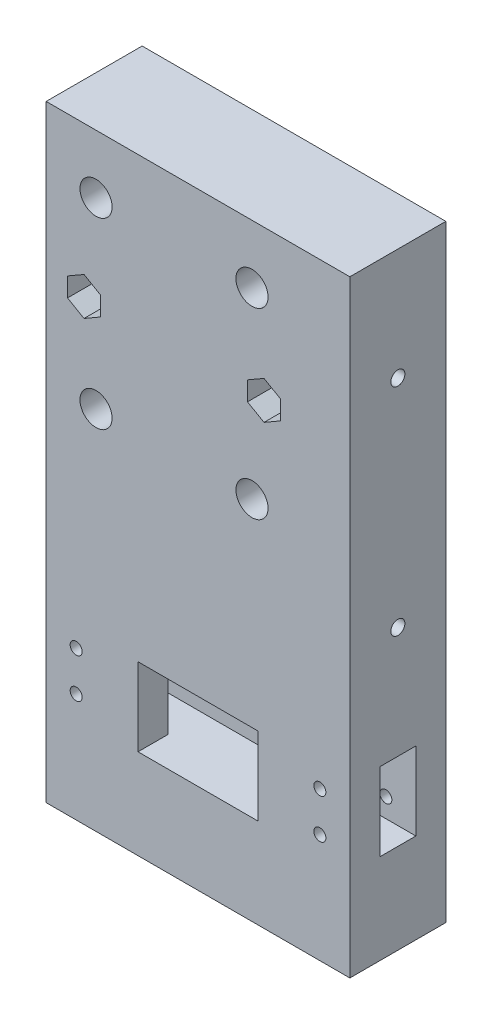
SolidWorks part; units mm, degrees
other "Markup1"
sketch "Sketch8" plane through (21.3115, 25, 0) normal (0.306, 0.1864, -0.9336) x (-0.9512, 0.0181, -0.3081)
ref_plane "Front Plane" through (0, 0, 0) normal (0, 0, 1) x (1, 0, 0)
ref_plane "Top Plane" through (0, 0, 0) normal (0, 1, 0) x (1, 0, 0)
ref_plane "Right Plane" through (0, 0, 0) normal (1, 0, 0) x (0, 0, -1)
sketch "Sketch1" plane through (0, 0, 0) normal (0, 0, 1) x (1, 0, 0)
  line L0 (0, 25) -> (0, -25) construction
  line L1 (21.3115, 25) -> (-21.3115, 25)
  line L2 (21.3115, 25) -> (21.3115, -25)
  line L3 (21.3115, -25) -> (-21.3115, -25)
  line L4 (-21.3115, 25) -> (-21.3115, -25)
  line L5 (21.3115, 25) -> (-21.3115, -25) construction
  line L6 (21.3115, -25) -> (-21.3115, 25) construction
  line L7 (-21.3115, 0) -> (21.3115, 0) construction
  circle A0 centre (-13, -15.25) radius 2.677
  circle A1 centre (13, -15.25) radius 2.677
  circle A2 centre (13, 15.25) radius 2.677
  circle A3 centre (-13, 15.25) radius 2.677
  point P0 (0, 0)
  dimension "D1" = 30.5
  dimension "D2" = 26
  dimension "D3" = 50
extrude "Boss-Extrude1" add sketch "Sketch1" along normal blind 16
sketch "Sketch2" plane through (0, 0, 0) normal (0, 0, 1) x (1, 0, 0)
  circle A0 centre (0, 0) radius 11
  dimension "D1" = 22
extrude "Cut-Extrude2" cut sketch "Sketch2" along normal blind 11
sketch "Sketch3" plane through (0, 0, 0) normal (0, 0, -1) x (-1, 0, 0)
  line L0 (0, 0) -> (-18.0234, 0) construction
  line L1 (0, 0) -> (0, 5.0894) construction
  circle A0 centre (-15, 0) radius 1.75
  circle A1 centre (15, 0) radius 1.75
  dimension "D1" = 15
  dimension "D2" = 3.5
extrude "Cut-Extrude3" cut sketch "Sketch3" against normal blind 10
sketch "Sketch9" plane through (0, 0, 0) normal (0, 0, -1) x (-1, 0, 0)
  line L0 (0, -11) -> (0, 11) construction
  line L1 (-15, 3.1754) -> (-17.75, 1.5877)
  line L2 (-17.75, 1.5877) -> (-17.75, -1.5877)
  line L3 (-17.75, -1.5877) -> (-15, -3.1754)
  line L4 (-15, -3.1754) -> (-12.25, -1.5877)
  line L5 (-12.25, -1.5877) -> (-12.25, 1.5877)
  line L6 (-12.25, 1.5877) -> (-15, 3.1754)
  line L7 (12.25, 1.5877) -> (15, 3.1754)
  line L8 (12.25, -1.5877) -> (12.25, 1.5877)
  line L9 (15, -3.1754) -> (12.25, -1.5877)
  line L10 (17.75, -1.5877) -> (15, -3.1754)
  line L11 (17.75, 1.5877) -> (17.75, -1.5877)
  line L12 (15, 3.1754) -> (17.75, 1.5877)
  circle A0 centre (-15, 0) radius 2.75 construction
  circle A1 centre (0, 0) radius 11 construction
  point P1 (-17.75, 0)
  dimension "D1" = 5.5
extrude "Cut-Extrude6" cut sketch "Sketch9" against normal through all from offset 5 offset against normal yes
sketch "Sketch30" plane through (0, -25, 0) normal (0, -1, 0) x (1, 0, 0)
  line L1 (-21.3115, 16) -> (21.3115, 16)
  line L2 (-21.3115, 16) -> (-21.3115, 0)
  line L3 (-21.3115, 0) -> (21.3115, 0)
  line L4 (21.3115, 16) -> (21.3115, 0)
extrude "Boss-Extrude8" add sketch "Sketch30" along normal blind 20.23
sketch "Sketch10" plane through (0, 0, 0) normal (0, 0, 1) x (1, 0, 0)
  line L0 (21.3115, -45.23) -> (-21.3115, -45.23)
  line L2 (-21.3115, -45.23) -> (-21.3115, -61.23)
  line L3 (-21.3115, -61.23) -> (21.3115, -61.23)
  line L4 (21.3115, -61.23) -> (21.3115, -45.23)
  dimension "D1" = 16
extrude "Boss-Extrude2" add sketch "Sketch10" along normal up to surface (16 mm away) up to face at (15, 0, 16)
sketch "Sketch14" plane through (-21.3115, 0, 0) normal (-1, 0, 0) x (0, 0, 1)
  line L0 (16, -61.23) -> (0, -61.23) construction
  line L1 (5, -61.23) -> (11, -61.23)
  line L2 (5, -61.23) -> (5, -48.23)
  line L3 (5, -48.23) -> (11, -48.23)
  line L4 (11, -61.23) -> (11, -48.23)
  line L7 (0, -61.23) -> (16, -61.23) construction
  point P6 (8, -61.23)
  point P7 (8, -61.23)
  dimension "D1" = 13
  dimension "D2" = 6
extrude "Cut-Extrude7" cut sketch "Sketch14" against normal through all
sketch "Sketch16" plane through (21.3115, 0, 0) normal (1, 0, 0) x (0, 0, -1)
  line L0 (-8, -48.23) -> (-8, 25)
  line L1 (-11, -48.23) -> (-5, -48.23) construction
  line L2 (-16, 25) -> (0, 25) construction
  line L4 (-16, 25) -> (0, 25)
  line L5 (-16, 25) -> (-16, -48.23)
  line L6 (-16, -48.23) -> (0, -48.23)
  line L7 (0, 25) -> (0, -48.23)
  line M6 (-11, -48.23) -> (-5, -48.23)
  line M9 (0, -61.23) -> (0, 25)
  line M10 (0, 25) -> (-16, 25)
  line M11 (-16, 25) -> (-16, -61.23)
extrude "Boss-Extrude3" add sketch "Sketch16" along normal blind 8 contours L6 L0 M11 M6 M10 | L6 L0 M6 M9 M10 region at (21.3115, -11.615, 12) region at (21.3115, -11.615, 4)
sketch "Sketch17" plane through (29.3115, 0, 0) normal (1, 0, 0) x (0, 0, -1)
  line L0 (-8, -48.23) -> (-8, 25)
  line L1 (-16, -48.23) -> (0, -48.23) construction
  line L2 (0, 25) -> (-16, 25) construction
  line L3 (-8, -11.615) -> (0, -11.615)
  line L4 (0, -48.23) -> (0, 25) construction
  circle A0 centre (-8, 6.385) radius 1.175
  circle A1 centre (-8, -29.615) radius 1.175
  point P8 (-8, -11.615)
  dimension "D2" = 2.35
  dimension "D1" = 18
extrude "Cut-Extrude9" cut sketch "Sketch17" against normal blind 8 contours L0 A0 | L0 A0 | A1 L0 | A1 L0 region at (29.3115, -29.615, 8.4987) region at (29.3115, 6.385, 8.4987) region at (29.3115, 6.385, 7.5013) region at (29.3115, -29.615, 7.5013)
sketch "Sketch18" plane through (0, 0, 0) normal (0, 0, -1) x (-1, 0, 0)
  line L0 (-25.3115, -48.23) -> (-25.3115, 25)
  line L1 (-29.3115, -48.23) -> (-21.3115, -48.23) construction
  line L2 (-29.3115, 25) -> (21.3115, 25) construction
  line L3 (-25.3115, -11.615) -> (-29.3115, -11.615)
  line L4 (-26.2115, 8.385) -> (-24.4115, 8.385)
  line L5 (-26.2115, 8.385) -> (-26.2115, 4.385)
  line L6 (-26.2115, 4.385) -> (-24.4115, 4.385)
  line L7 (-24.4115, 8.385) -> (-24.4115, 4.385)
  line L8 (-26.2115, 8.385) -> (-24.4115, 4.385) construction
  line L9 (-26.2115, 4.385) -> (-24.4115, 8.385) construction
  line L10 (-29.3115, -48.23) -> (-29.3115, 25) construction
  line L11 (-26.2115, -27.615) -> (-24.4115, -27.615)
  line L12 (-24.4115, -31.615) -> (-24.4115, -27.615)
  line L13 (-26.2115, -31.615) -> (-24.4115, -31.615)
  line L14 (-26.2115, -31.615) -> (-26.2115, -27.615)
  point P6 (-25.3115, 6.385)
  point P11 (-25.3115, -11.615)
  dimension "D1" = 18
  dimension "D2" = 4
  dimension "D3" = 1.8
extrude "Cut-Extrude10" cut sketch "Sketch18" against normal blind 10.2 contours L7 L4 L0 L6 | L5 L6 L0 L4 | L14 L11 L12 L13 region at (25.7615, 6.385, 0) region at (24.8615, 6.385, 0)
sketch "Sketch15" plane through (0, 0, 0) normal (0, 0, -1) x (-1, 0, 0)
  line L0 (21.3115, -61.23) -> (-21.3115, -61.23) construction
  line L1 (-29.3115, -23.2996) -> (21.3115, -23.2996)
  line L2 (-21.3115, -61.23) -> (-21.3115, -48.23)
  line L3 (-29.3115, -48.23) -> (-29.3115, 25) construction
  line L4 (-4, -23.2996) -> (-4, -61.23)
  line L7 (-21.3115, -61.23) -> (-21.3115, -48.23) construction
  line L8 (-21.3115, -48.23) -> (-21.3115, -61.23) construction
  line L9 (-21.3115, -54.73) -> (21.3115, -54.73)
  line L10 (21.3115, 25) -> (21.3115, -61.23) construction
  line L11 (21.3115, -54.73) -> (21.3115, -28)
  line L12 (21.3115, -28) -> (0, -28)
  line L13 (0, -28) -> (0, -61.23)
  circle A2 centre (16.3115, -58.03) radius 1
  circle A4 centre (16.3115, -51.43) radius 1
  point P11 (-21.3115, -61.23)
  dimension "D1" = 5
  dimension "D2" = 3.2
extrude "Cut-Extrude8" cut sketch "Sketch15" against normal through all and the other way through all contours A2 | A4
sketch "Sketch6" plane through (0, -48.23, 0) normal (0, -1, 0) x (1, 0, 0)
  line L0 (21.3115, 11) -> (-21.3115, 11) construction
  line L1 (4.517, 11) -> (-4.517, 11)
  line L2 (4.517, 11) -> (4.517, 14.85)
  line L3 (4.517, 14.85) -> (-4.517, 14.85)
  line L4 (-4.517, 11) -> (-4.517, 14.85)
  line L5 (4.517, 11) -> (-4.517, 14.85) construction
  line L6 (4.517, 14.85) -> (-4.517, 11) construction
  point P0 (0, 12.925)
  dimension "D1" = 3.85
extrude "Cut-Extrude5" cut sketch "Sketch6" against normal blind 50 and the other way through all
sketch "Sketch20" plane through (0, -48.23, 0) normal (0, -1, 0) x (-1, 0, 0)
  line L1 (-21.3115, -16) -> (-29.3115, -16)
  line L2 (-21.3115, -16) -> (-21.3115, 0)
  line L3 (-21.3115, 0) -> (-29.3115, 0)
  line L4 (-29.3115, -16) -> (-29.3115, 0)
extrude "Boss-Extrude5" add sketch "Sketch20" along normal up to surface (13 mm away) up to face at (0, -61.23, 13.2125)
sketch "Sketch21" plane through (0, -61.23, 0) normal (0, -1, 0) x (-1, 0, 0)
  line L0 (-29.3115, -16) -> (-29.3115, 0) construction
  line L1 (-21.3115, -11) -> (-29.3115, -11)
  line L2 (-21.3115, -11) -> (-21.3115, -5)
  line L3 (-21.3115, -5) -> (-29.3115, -5)
  line L4 (-29.3115, -11) -> (-29.3115, -5)
extrude "Cut-Extrude11" cut sketch "Sketch21" against normal up to surface (13 mm away) up to face at (0, -48.23, 9)
sketch "Sketch22" plane through (0, 0, 0) normal (0, 0, -1) x (-1, 0, 0)
  line L0 (21.3115, -61.23) -> (-29.3115, -61.23) construction
  line L1 (-29.3115, -61.23) -> (-29.3115, 25) construction
  circle A0 centre (-24.3115, -58.03) radius 1
  circle A3 centre (-24.3115, -51.43) radius 1
  dimension "D1" = 2
  dimension "D2" = 3.2
  dimension "D3" = 5
  dimension "D4" = 6.6
  dimension "D5" = 2
  dimension "D6" = 5
extrude "Cut-Extrude12" cut sketch "Sketch22" against normal through all
sketch "Sketch24" plane through (0, -61.23, 0) normal (0, -1, 0) x (1, 0, 0)
  line L1 (-21.3115, 5) -> (29.3115, 5)
  line L2 (-21.3115, 5) -> (-21.3115, 0)
  line L3 (-21.3115, 0) -> (29.3115, 0)
  line L4 (29.3115, 5) -> (29.3115, 0)
extrude "Boss-Extrude6" add sketch "Sketch24" along normal blind 15
sketch "Sketch25" plane through (0, 0, 5) normal (0, 0, 1) x (1, 0, 0)
  line L0 (29.3115, -76.23) -> (-21.3115, -76.23) construction
  line L1 (-21.3115, -76.23) -> (29.3115, -76.23)
  line L2 (-21.3115, -76.23) -> (-21.3115, -61.23)
  line L3 (-21.3115, -61.23) -> (29.3115, -61.23)
  line L4 (29.3115, -76.23) -> (29.3115, -61.23)
extrude "Boss-Extrude7" add sketch "Sketch25" along normal up to surface (11 mm away) up to face at (23.3115, -58.03, 16)
sketch "Sketch26" plane through (0, -76.23, 0) normal (0, -1, 0) x (1, 0, 0)
  line L0 (4, 16) -> (4, 0)
  line L1 (29.3115, 16) -> (-21.3115, 16) construction
  line L2 (-21.3115, 0) -> (29.3115, 0) construction
  line L3 (4, 8) -> (-21.3115, 8)
  line L4 (-21.3115, 16) -> (-21.3115, 0) construction
  circle A0 centre (-14, 8) radius 1
  circle A1 centre (22, 8) radius 1
  dimension "D1" = 2
  dimension "D2" = 18
extrude "Cut-Extrude13" cut sketch "Sketch26" against normal blind 10 contours L3 A0 | L3 A0 | A1 region at (-14, -76.23, 7.5756) region at (-14, -76.23, 8.4244) region at (22, -76.23, 8)
sketch "Sketch27" plane through (0, 0, 0) normal (0, 0, -1) x (-1, 0, 0)
  line L0 (-24.4115, -31.615) -> (-24.4115, -27.615) construction
  line L1 (-24.0015, -71.33) -> (-20.0015, -71.33)
  line L2 (-24.0015, -71.33) -> (-24.0015, -73.13)
  line L3 (-24.0015, -73.13) -> (-20.0015, -73.13)
  line L4 (-20.0015, -71.33) -> (-20.0015, -73.13)
  line L5 (-24.0015, -71.33) -> (-20.0015, -73.13) construction
  line L6 (-24.0015, -73.13) -> (-20.0015, -71.33) construction
  line L8 (-26.2115, -31.615) -> (-24.4115, -31.615) construction
  line L12 (-29.3115, -76.23) -> (-29.3115, 25) construction
  line L13 (21.3115, -76.23) -> (-29.3115, -76.23) construction
  line L14 (-29.3115, -49.5626) -> (21.3115, -49.5626)
  line L15 (21.3115, 25) -> (21.3115, -76.23) construction
  line L16 (-4, -49.5626) -> (-4, -76.23)
  line L17 (16.0015, -73.13) -> (12.0015, -73.13)
  line L18 (12.0015, -71.33) -> (12.0015, -73.13)
  line L19 (16.0015, -71.33) -> (12.0015, -71.33)
  line L20 (16.0015, -71.33) -> (16.0015, -73.13)
  point P0 (-22.0015, -72.23)
  dimension "D1" = 7.31
  dimension "D2" = 3.1
extrude "Cut-Extrude14" cut sketch "Sketch27" against normal blind 10.2 contours L4 L1 L2 L3 | L20 L19 L18 L17 region at (22.0015, -72.23, 0) region at (-14.0015, -72.23, 0)
sketch "Sketch29" plane through (0, 0, 16) normal (0, 0, 1) x (1, 0, 0)
  line L0 (-16.3115, -51.43) -> (24.3115, -58.03)
  line L1 (24.3115, -51.43) -> (-16.3115, -58.03)
  line L2 (-16.3115, -51.43) -> (24.3115, -51.43)
  line L3 (-16.3115, -51.43) -> (-16.3115, -58.03)
  line L4 (-16.3115, -58.03) -> (24.3115, -58.03)
  line L5 (24.3115, -51.43) -> (24.3115, -58.03)
  line L7 (-6, -48.23) -> (14, -48.23)
  line L8 (-6, -48.23) -> (-6, -61.23)
  line L9 (-6, -61.23) -> (14, -61.23)
  line L10 (14, -48.23) -> (14, -61.23)
  line L11 (-6, -48.23) -> (14, -61.23) construction
  line L12 (-6, -61.23) -> (14, -48.23) construction
  circle A0 centre (-16.3115, -51.43) radius 1 construction
  point P4 (4, -54.73)
  dimension "D1" = 13
  dimension "D2" = 20
extrude "Cut-Extrude15" cut sketch "Sketch29" against normal up to surface (5 mm away) contours L10 L7 L8 L2 | L10 L2 L8 L0 L1 | L0 L8 L1 | L10 L4 L8 L9 | L10 L0 L1 L8 L4 | L10 L1 L0 region at (4, -52.718, 16) region at (-2.6667, -54.73, 16) region at (4, -49.83, 16) region at (10.6667, -54.73, 16) region at (4, -56.742, 16) region at (4, -59.63, 16) up to face at (-16.3115, -59.03, 11)
